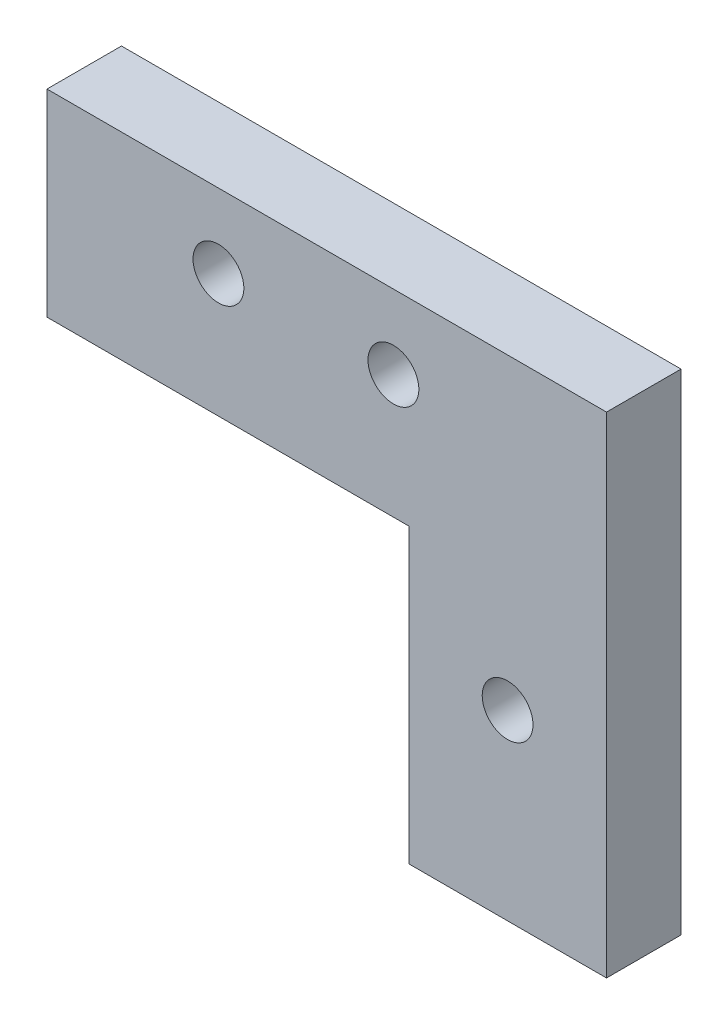
SolidWorks part; units mm, degrees
material "Rubber"
ref_plane "Front Plane" through (0, 0, 0) normal (0, 0, 1) x (1, 0, 0)
ref_plane "Top Plane" through (0, 0, 0) normal (0, 1, 0) x (1, 0, 0)
ref_plane "Right Plane" through (0, 0, 0) normal (1, 0, 0) x (0, 0, -1)
sketch "Sketch1" plane through (0, 0, 0) normal (0, 0, 1) x (1, 0, 0)
  line L1 (0, 0) -> (14, 0)
  line L2 (0, 0) -> (0, -34.73)
  line L3 (0, -34.73) -> (14, -34.73)
  line L4 (14, 0) -> (14, -34.73)
  line L5 (0, 0) -> (-25.65, 0)
  line L6 (0, 0) -> (0, -14)
  line L7 (0, -14) -> (-25.65, -14)
  line L8 (-25.65, 0) -> (-25.65, -14)
  dimension "D1" = 14
  dimension "D2" = 39.65
  dimension "D3" = 34.73
extrude "Boss-Extrude1" add sketch "Sketch1" along normal blind 42.65 contours L5 L8 L7 L2 | L4 L1 L2 L3 region at (7, -17.365, 0) region at (-12.825, -7, 0)
sketch "Sketch2" plane through (0, -14, 0) normal (0, -1, 0) x (1, 0, 0)
  line L0 (-25.65, 42.65) -> (-25.65, 0) construction
  line L1 (0, 42.65) -> (-25.65, 42.65) construction
  circle A0 centre (-14.665, 27.725) radius 6.425
  point P2 (-21.09, 27.725)
  point P6 (-14.665, 34.15)
  dimension "D1" = 12.85
  dimension "D2" = 4.56
  dimension "D3" = 8.5
extrude "Cut-Extrude1" cut sketch "Sketch2" against normal blind 42.65
sketch "Sketch3" plane through (0, -14, 0) normal (0, -1, 0) x (1, 0, 0)
  line L0 (0, 42.65) -> (-25.65, 42.65) construction
  line L1 (-17.65, 42.65) -> (-15.75, 42.65)
  line L2 (-17.65, 42.65) -> (-17.65, 12.65)
  line L3 (-17.65, 12.65) -> (-15.75, 12.65)
  line L4 (-15.75, 42.65) -> (-15.75, 12.65)
  line L5 (-25.65, 42.65) -> (-25.65, 0) construction
  dimension "D1" = 8
  dimension "D2" = 1.9
  dimension "D3" = 30
extrude "Cut-Extrude2" cut sketch "Sketch3" against normal blind 42.65
sketch "Sketch4" plane through (0, 0, 0) normal (-1, 0, 0) x (0, 0, 1)
  line L0 (42.65, -34.73) -> (0, -34.73) construction
  line L1 (42.65, -14) -> (42.65, -34.73) construction
  circle A0 centre (18.725, -21.745) radius 6.425
  point P2 (25.15, -21.745)
  point P3 (18.725, -28.17)
  dimension "D1" = 12.85
  dimension "D2" = 6.56
  dimension "D3" = 17.5
extrude "Cut-Extrude3" cut sketch "Sketch4" against normal blind 42.65
sketch "Sketch5" plane through (0, 0, 0) normal (-1, 0, 0) x (0, 0, 1)
  line L0 (42.65, -14) -> (42.65, -34.73) construction
  line L1 (42.65, -26.73) -> (10.65, -26.73)
  line L2 (42.65, -26.73) -> (42.65, -24.83)
  line L3 (42.65, -24.83) -> (10.65, -24.83)
  line L4 (10.65, -26.73) -> (10.65, -24.83)
  line L5 (42.65, -34.73) -> (0, -34.73) construction
  dimension "D1" = 8
  dimension "D2" = 1.9
  dimension "D3" = 32
extrude "Cut-Extrude4" cut sketch "Sketch5" against normal blind 42.65
hole_wizard "M3 Clearance Hole1" positions "Sketch6" profile "Sketch8" hole size "M3" standard "ANSI Metric"
sketch "Sketch6" plane through (0, 0, 0) normal (0, 0, -1) x (-1, 0, 0)
  line L0 (-14, 0) -> (25.65, 0) construction
  line L1 (25.65, 0) -> (25.65, -14) construction
  line L2 (-14, 0) -> (-14, -34.73) construction
  point P0 (1.1, -5.25)
  point P2 (13.5, -5.25)
  point P4 (-6.99, -21.8)
  dimension "D1" = 12.4
  dimension "D2" = 5.25
  dimension "D3" = 12.15
  dimension "D4" = 7.01
  dimension "D5" = 21.8
sketch "Sketch8" plane through (-1.1, -5.25, 0) normal (1, 0, 0) x (0, 1, 0)
  line L0 (0, 0) -> (0, 11.0815)
  line L1 (0, 11.0815) -> (1.8, 10)
  line L2 (1.8, 10) -> (1.8, 0.025)
  line L3 (1.8, 0.025) -> (1.825, 0)
  line L5 (1.825, 0) -> (0, 0)
  line L6 (-1.8, 0.025) -> (-1.825, 0) construction
  line L10 (0, 11.0815) -> (-1.8, 10) construction
  line L11 (0, -6.35) -> (0, 107.95) construction
  dimension "Hole Dia." = 3.6
  dimension "Hole Depth" = 10
  dimension "Near C'Sink Dia." = 3.65
  dimension "Near C'Sink Angle" = 90
  dimension "Drill Angle" = 118
ref_axis "Axis1" through (-14.665, 0.9766, 27.725) along (0, -1, 0)
ref_point "Point1"
ref_plane "Plane2" through (-14.665, 0, 0) normal (-1, 0, 0) x (0, 0, 1)
ref_point "Point2"
ref_plane "Plane3" through (0, 0, 18.725) normal (0, 0, -1) x (-1, 0, 0)
sketch "Sketch9" plane through (0, 0, 0) normal (0, 1, 0) x (1, 0, 0)
  line L0 (14, 0) -> (-25.65, 0) construction
  line L1 (-36.4186, -5.28) -> (25.575, -5.28)
  line L2 (-36.4186, -5.28) -> (-36.4186, -45.8335)
  line L3 (-36.4186, -45.8335) -> (25.575, -45.8335)
  line L4 (25.575, -5.28) -> (25.575, -45.8335)
  dimension "D1" = 5.28
extrude "Cut-Extrude5" cut sketch "Sketch9" against normal through all
